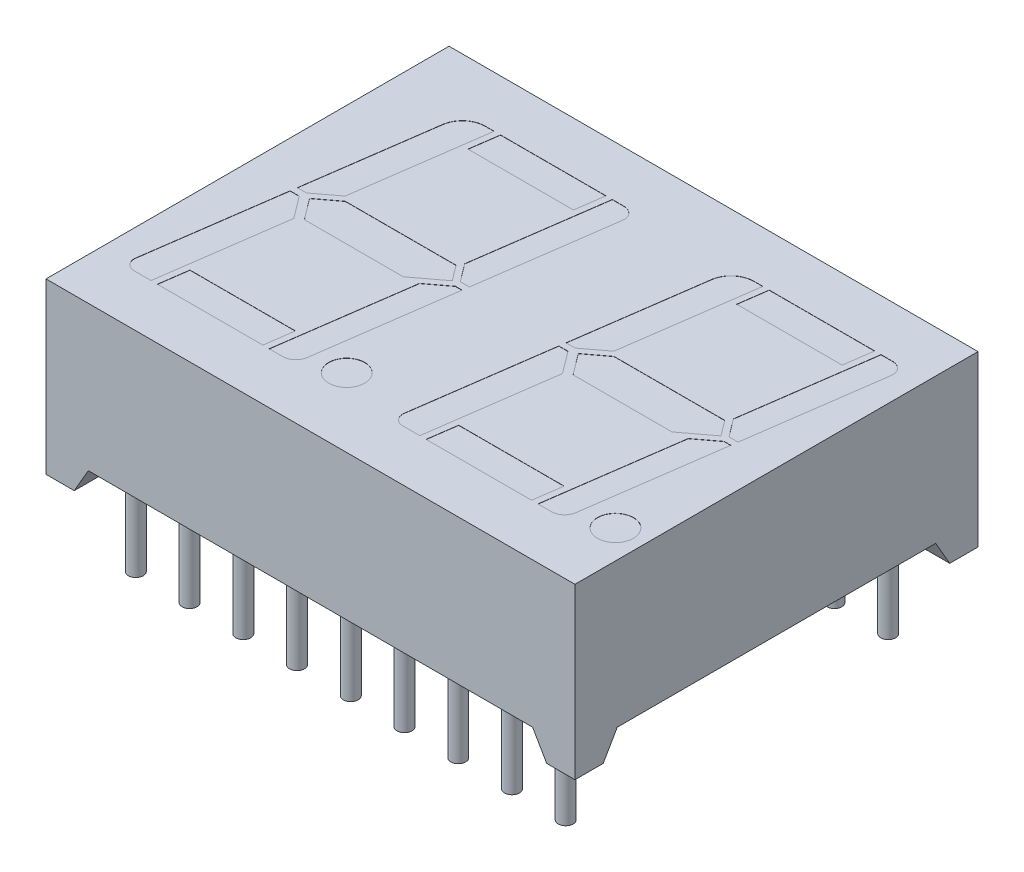
SolidWorks part; units mm, degrees
ref_plane "Front Plane" through (0, 0, 0) normal (0, 0, 1) x (1, 0, 0)
ref_plane "Top Plane" through (0, 0, 0) normal (0, 1, 0) x (1, 0, 0)
ref_plane "Right Plane" through (0, 0, 0) normal (1, 0, 0) x (0, 0, -1)
sketch "Sketch1" plane through (0, 0, 0) normal (0, 1, 0) x (1, 0, 0)
  line L1 (12.5, -9.525) -> (-12.5, -9.525)
  line L2 (12.5, -9.525) -> (12.5, 9.525)
  line L3 (12.5, 9.525) -> (-12.5, 9.525)
  line L4 (-12.5, -9.525) -> (-12.5, 9.525)
  line L5 (12.5, -9.525) -> (-12.5, 9.525) construction
  line L6 (12.5, 9.525) -> (-12.5, -9.525) construction
  point P0 (0, 0)
  dimension "D1" = 19.05
  dimension "D2" = 25
extrude "Boss-Extrude1" add sketch "Sketch1" along normal blind 8
sketch "Sketch2" plane through (0, 0, 9.525) normal (0, 0, 1) x (1, 0, 0)
  line L0 (-11.164, 0) -> (-10.5, 1.15)
  line L1 (-12.5, 0) -> (12.5, 0) construction
  line L2 (-10.5, 1.15) -> (10.5, 1.15)
  line L3 (0, 0) -> (0, 8) construction
  line L4 (-12.5, 8) -> (12.5, 8) construction
  line L5 (11.164, 0) -> (10.5, 1.15)
  line L6 (-12.5, 8) -> (-12.5, 0) construction
  point P12 (0, 1.15)
  dimension "D1" = 2
  dimension "D2" = 120
  dimension "D3" = 1.15
extrude "Cut-Extrude1" cut sketch "Sketch2" along direction (0, 0, 1) on the side against the normal through all
sketch "Sketch3" plane through (0, 8, 0) normal (0, 1, 0) x (1, 0, 0)
  line L0 (0, -9.525) -> (0, 9.525) construction
  line L1 (-12.5, -9.525) -> (12.5, -9.525) construction
  line L2 (12.5, 9.525) -> (-12.5, 9.525) construction
  line L3 (0, 0) -> (-12.5, 0) construction
  line L4 (-3.1842, -7.11) -> (0, -7.11) construction
  line L5 (-12.5, 9.525) -> (-12.5, -9.525) construction
  line L6 (-10.2939, 0.15) -> (-9.4466, 6.1791)
  line L7 (-11.3142, -7.11) -> (-3.1842, -7.11) construction
  line L8 (-11.3142, -7.11) -> (-9.3158, 7.11) construction
  line L9 (-9.3158, 7.11) -> (-1.1858, 7.11) construction
  line L10 (-3.1842, -7.11) -> (-1.1858, 7.11) construction
  line L11 (-11.3142, -7.11) -> (-1.1858, 7.11) construction
  line L12 (-9.3158, 7.11) -> (-3.1842, -7.11) construction
  line L13 (-7.9525, 7.11) -> (-8.8203, 0.9351)
  line L14 (-7.9525, 7.11) -> (-8.3757, 7.11)
  line L15 (-10.2939, 0.15) -> (-9.8622, 0.15)
  line L16 (-9.8622, 0.15) -> (-8.8203, 0.9351)
  line L17 (-6.25, 0.2145) -> (-6.25, 0.8985) construction
  line L18 (-2.3672, 7.11) -> (-1.8135, 7.11)
  line L19 (-7.6525, 7.11) -> (-2.6672, 7.11)
  line L20 (-7.6525, 7.11) -> (-7.8422, 5.76)
  line L21 (-7.8422, 5.76) -> (-2.8569, 5.76)
  line L22 (-2.6672, 7.11) -> (-2.8569, 5.76)
  line L23 (-1.2731, 6.4884) -> (-2.1639, 0.15)
  line L24 (-2.3672, 7.11) -> (-3.2272, 0.9904)
  line L25 (-3.2272, 0.9904) -> (-2.5939, 0.15)
  line L26 (-2.5939, 0.15) -> (-2.1639, 0.15)
  line L27 (-8.6046, 0.7266) -> (-3.37, 0.7266)
  line L28 (-8.6046, 0.7266) -> (-9.5688, 0)
  line L29 (-3.37, 0.7266) -> (-2.8225, 0)
  line L30 (-10.3361, -0.15) -> (-9.9043, -0.15)
  line L31 (-9.9043, -0.15) -> (-9.1192, -1.1919)
  line L32 (-9.1192, -1.1919) -> (-9.951, -7.11)
  line L33 (-9.951, -7.11) -> (-10.7505, -7.11)
  line L34 (-10.3361, -0.15) -> (-11.2358, -6.5517)
  line L35 (-9.8622, 0.15) -> (-9.756, 0.9057) construction
  line L36 (-2.8225, 0) -> (-4.1425, -0.9947)
  line L37 (-9.651, -7.11) -> (-4.6657, -7.11)
  line L38 (-9.651, -7.11) -> (-9.4612, -5.76)
  line L39 (-9.4612, -5.76) -> (-4.4759, -5.76)
  line L40 (-4.6657, -7.11) -> (-4.4759, -5.76)
  line L41 (-4.1425, -0.9947) -> (-8.8192, -0.9947)
  line L42 (-8.8192, -0.9947) -> (-9.5688, 0)
  line L43 (-2.2061, -0.15) -> (-3.1083, -6.5694)
  line L44 (-3.7302, -7.11) -> (-4.3657, -7.11)
  line L45 (-4.3657, -7.11) -> (-3.4899, -0.8786)
  line L46 (-3.4899, -0.8786) -> (-2.523, -0.15)
  line L47 (-2.523, -0.15) -> (-2.2061, -0.15)
  circle A0 centre (-1.55, -6.26) radius 0.85
  arc A1 (-9.4466, 6.1791) -> (-8.3757, 7.11) centre (-8.3757, 6.0286) cw
  arc A2 (-1.8135, 7.11) -> (-1.2731, 6.4884) centre (-1.8135, 6.5643) cw
  arc A3 (-11.2358, -6.5517) -> (-10.7505, -7.11) centre (-10.7505, -6.6199) ccw
  arc A4 (-3.7302, -7.11) -> (-3.1083, -6.5694) centre (-3.7302, -6.482) ccw
  point P12 (-6.25, 0)
  dimension "D1" = 4.7
  dimension "D2" = 14.22
  dimension "D3" = 8.13
  dimension "D4" = 1.35
  dimension "D5" = 8
  dimension "D6" = 135
  dimension "D7" = 0.4318
  dimension "D8" = 0.15
  dimension "D9" = 0.3
  dimension "D10" = 1.35
  dimension "D11" = 0.15
  dimension "D12" = 0.3
  dimension "D13" = 0.43
  dimension "D14" = 135
  dimension "D15" = 0.3
  dimension "D16" = 0.3
  dimension "D17" = 135
  dimension "D18" = 1.35
  dimension "D19" = 0.3
  dimension "D20" = 0.15
  dimension "D21" = 135
  dimension "D22" = 0.3
  dimension "D23" = 0.3
  dimension "D24" = 0.15
extrude "Cut-Extrude3" cut sketch "Sketch3" against normal blind 0.01
pattern_linear "LPattern2" count 2 spacing 12.7 along (1, 0, 0) of "Cut-Extrude3"
sketch "Sketch4" plane through (-12.5, 0, 0) normal (-1, 0, 0) x (0, 0, 1)
  line L0 (-8.189, 0) -> (-7.525, 1.15)
  line L1 (-9.525, 0) -> (9.525, 0) construction
  line L2 (-7.525, 1.15) -> (7.525, 1.15)
  line L3 (0, 0) -> (0, 8) construction
  line L4 (-9.525, 8) -> (9.525, 8) construction
  line L5 (8.189, 0) -> (7.525, 1.15)
  line L6 (-9.525, 8) -> (-9.525, 0) construction
  point P12 (0, 1.15)
  dimension "D1" = 2
  dimension "D2" = 120
  dimension "D3" = 1.15
extrude "Cut-Extrude4" cut sketch "Sketch4" against normal through all
sketch "Sketch5" plane through (0, 1.15, 0) normal (0, -1, 0) x (1, 0, 0)
  line L0 (0, -9.525) -> (0, 9.525) construction
  line L1 (-10.5, -9.525) -> (10.5, -9.525) construction
  line L2 (10.5, 9.525) -> (-10.5, 9.525) construction
  line L3 (-12.5, 0) -> (12.5, 0) construction
  line L4 (-12.5, 7.525) -> (-12.5, -7.525) construction
  line L5 (12.5, -7.525) -> (12.5, 7.525) construction
  circle A0 centre (0, 7.62) radius 0.3509
  circle A1 centre (-2.54, 7.62) radius 0.3509
  circle A2 centre (-5.08, 7.62) radius 0.3509
  circle A3 centre (-7.62, 7.62) radius 0.3509
  circle A4 centre (-10.16, 7.62) radius 0.3509
  circle A5 centre (0, 7.62) radius 0.3509
  circle A6 centre (-2.54, 7.62) radius 0.3509
  circle A7 centre (-5.08, 7.62) radius 0.3509
  circle A8 centre (-7.62, 7.62) radius 0.3509
  circle A9 centre (2.54, 7.62) radius 0.3509
  circle A10 centre (0, 7.62) radius 0.3509
  circle A11 centre (-2.54, 7.62) radius 0.3509
  circle A12 centre (-5.08, 7.62) radius 0.3509
  circle A13 centre (5.08, 7.62) radius 0.3509
  circle A14 centre (2.54, 7.62) radius 0.3509
  circle A15 centre (0, 7.62) radius 0.3509
  circle A16 centre (-2.54, 7.62) radius 0.3509
  circle A17 centre (7.62, 7.62) radius 0.3509
  circle A18 centre (5.08, 7.62) radius 0.3509
  circle A19 centre (2.54, 7.62) radius 0.3509
  circle A20 centre (0, 7.62) radius 0.3509
  circle A21 centre (2.54, 7.62) radius 0.3509
  circle A22 centre (5.08, 7.62) radius 0.3509
  circle A23 centre (7.62, 7.62) radius 0.3509
  circle A24 centre (10.16, 7.62) radius 0.3509
  circle A25 centre (10.16, -7.62) radius 0.3509
  circle A26 centre (7.62, -7.62) radius 0.3509
  circle A27 centre (5.08, -7.62) radius 0.3509
  circle A28 centre (2.54, -7.62) radius 0.3509
  circle A29 centre (-10.16, -7.62) radius 0.3509
  circle A30 centre (-7.62, -7.62) radius 0.3509
  circle A31 centre (-5.08, -7.62) radius 0.3509
  circle A32 centre (-2.54, -7.62) radius 0.3509
  circle A33 centre (0, -7.62) radius 0.3509
  dimension "D1" = 0.7018
  dimension "D4" = 7.62
  dimension "D2" = 5
  dimension "D3" = 5
extrude "Boss-Extrude2" add sketch "Sketch5" along normal blind 4.91 contours A4 | A3 | A2 | A1 | A0 | A9 | A13 | A17 | A24 | A25 | A26 | A27 | A28 | A33 | A32 | A31 | A30 | A29
equation "\"D2@Sketch3\"  =14.22 /2"
equation "\"SegmentSpace\"=0.3"
equation "\"D8@Sketch3\"=\"SegmentSpace\" /2"
equation "\"D9@Sketch3\"=\"SegmentSpace\""
equation "\"SegmentWidth\"=1.35"
equation "\"D4@Sketch3\"=\"SegmentWidth\""
equation "\"D10@Sketch3\"=\"SegmentWidth\""
equation "\"D11@Sketch3\"=\"SegmentSpace\" /2"
equation "\"D12@Sketch3\"=\"SegmentSpace\""
equation "\"D15@Sketch3\"=\"SegmentSpace\""
equation "\"D16@Sketch3\"=\"SegmentSpace\""
equation "\"D18@Sketch3\"=\"SegmentWidth\""
equation "\"D19@Sketch3\"=\"SegmentSpace\""
equation "\"D20@Sketch3\"=\"SegmentSpace\" / 2"
equation "\"D22@Sketch3\"=\"SegmentSpace\""
equation "\"D23@Sketch3\"=\"SegmentSpace\""
equation "\"D24@Sketch3\"=\"SegmentSpace\" /2"
equation "\"D25@Sketch3\" = \"SegmentSpace\""
equation "\"D4@Sketch5\"=15.24 / 2"
